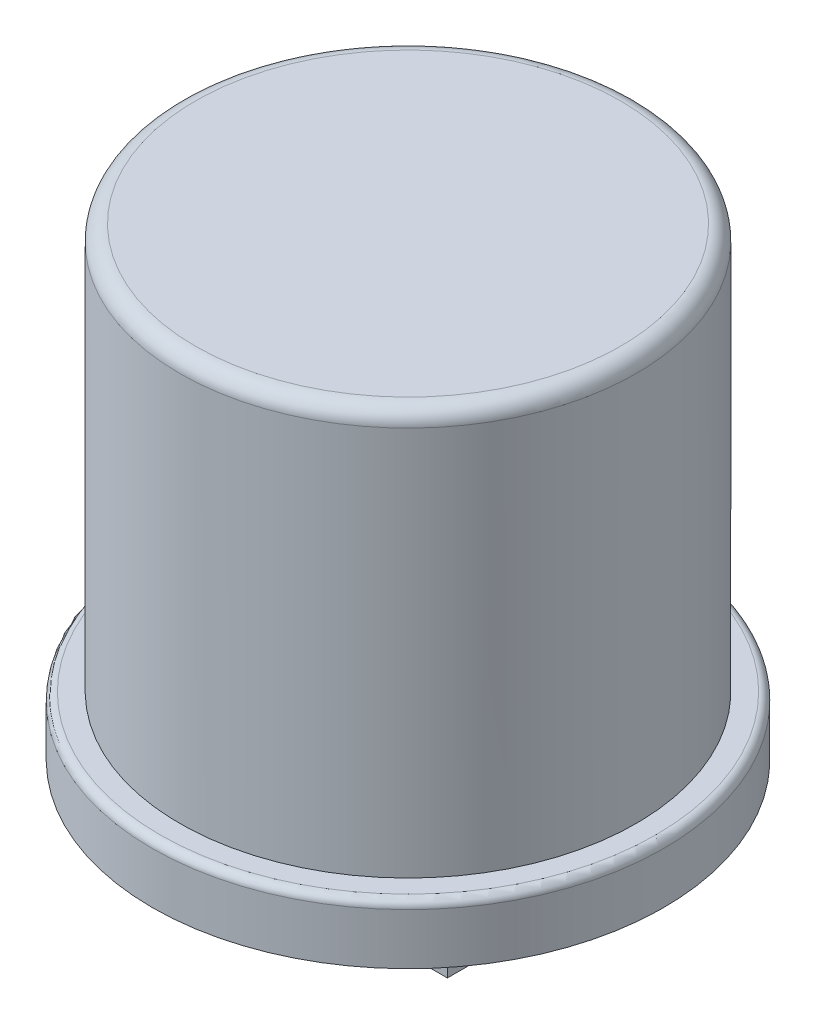
SolidWorks part; units mm, degrees
ref_plane "Front Plane" through (0, 0, 0) normal (0, 0, 1) x (1, 0, 0)
ref_plane "Top Plane" through (0, 0, 0) normal (0, 1, 0) x (1, 0, 0)
ref_plane "Right Plane" through (0, 0, 0) normal (1, 0, 0) x (0, 0, -1)
sketch "Sketch1" plane through (0, 0, 0) normal (0, 1, 0) x (1, 0, 0)
  circle A0 centre (0, 0) radius 6.5
  dimension "D1" = 13
extrude "Boss-Extrude1" add sketch "Sketch1" along normal blind 1.5
sketch "Sketch2" plane through (0, 1.5, 0) normal (0, 1, 0) x (1, 0, 0)
  circle A0 centre (0, 0) radius 5.8
  dimension "D1" = 11.6
extrude "Boss-Extrude2" add sketch "Sketch2" along normal blind 10.3
fillet "Fillet1" radius 0.4 1 edges at (0, 11.8, 5.8)
sketch "Sketch3" plane through (0, 0, 0) normal (0, -1, 0) x (1, 0, 0)
  circle A0 centre (0, 0) radius 5
  dimension "D1" = 10
extrude "Cut-Extrude1" cut sketch "Sketch3" against normal blind 4.8
sketch "Sketch4" plane through (0, 4.8, 0) normal (0, -1, 0) x (1, 0, 0)
  line L0 (-4.991, 0.3) -> (-2.9, 0.3)
  line L1 (-4.991, -0.3) -> (-2.9, -0.3)
  line L2 (-5, 0) -> (5, 0) construction
  line L3 (-2.9, 0.3) -> (-2.9, -0.3)
  line L4 (0, -0.825) -> (0, 0.825) construction
  line L5 (2.9, 0.3) -> (2.9, -0.3)
  line L6 (4.991, -0.3) -> (2.9, -0.3)
  line L7 (4.991, 0.3) -> (2.9, 0.3)
  line L8 (0, 5) -> (0, -5) construction
  line L9 (-0.3, 4.991) -> (-0.3, 2.7)
  line L10 (0.3, 4.991) -> (0.3, 2.7)
  line L11 (0.3, 2.7) -> (-0.3, 2.7)
  line L12 (0.3, -2.7) -> (-0.3, -2.7)
  line L13 (0.3, -4.991) -> (0.3, -2.7)
  line L14 (-0.3, -4.991) -> (-0.3, -2.7)
  circle A0 centre (0, 0) radius 5 construction
  circle A1 centre (0, 0) radius 5 construction
  arc A2 (-0.3, -4.991) -> (0.3, -4.991) centre (0, 0) ccw
  circle A3 centre (0, 0) radius 5
  arc A4 (-4.991, 0.3) -> (-4.991, -0.3) centre (0, 0) ccw
  arc A5 (4.991, -0.3) -> (4.991, 0.3) centre (0, 0) ccw
  arc A6 (0.3, 4.991) -> (-0.3, 4.991) centre (0, 0) ccw
  point P11 (-2.9, 0)
  point P25 (0, 2.7)
  dimension "D1" = 5.8
  dimension "D2" = 0.6
  dimension "D3" = 5.4
  dimension "D4" = 0
extrude "Boss-Extrude3" add sketch "Sketch4" along normal up to surface (4.8 mm away) up to face at (0, 0, -5)
sketch "Sketch5" plane through (0, 4.8, 0) normal (0, -1, 0) x (1, 0, 0)
  line L0 (-2.9, 0.3) -> (-2.9, -0.3) construction
  line L1 (-1, 2.7) -> (1, 2.7)
  line L2 (-1, 2.7) -> (-1, 1.9)
  line L3 (-1, 1.9) -> (1, 1.9)
  line L4 (1, 2.7) -> (1, 1.9)
  line L5 (-2.9, 1.9) -> (-1.9, 1.9)
  line L6 (-2.9, 1.9) -> (-2.9, -1.9)
  line L7 (-2.9, -1.9) -> (-1.9, -1.9)
  line L8 (-1.9, 1.9) -> (-1.9, -1.9)
  line L9 (0.3, 2.7) -> (-0.3, 2.7) construction
  line L10 (0, -0.825) -> (0, 0.825) construction
  line L11 (1.9, 1.9) -> (1.9, -1.9)
  line L12 (2.9, -1.9) -> (1.9, -1.9)
  line L13 (2.9, 1.9) -> (2.9, -1.9)
  line L14 (2.9, 1.9) -> (1.9, 1.9)
  line L15 (0.825, 0) -> (-0.825, 0) construction
  line L16 (1, -2.7) -> (1, -1.9)
  line L17 (-1, -1.9) -> (1, -1.9)
  line L18 (-1, -2.7) -> (-1, -1.9)
  line L19 (-1, -2.7) -> (1, -2.7)
  point P4 (0, 2.7)
  point P10 (-1.9, 0)
  dimension "D1" = 3.8
  dimension "D2" = 2
  dimension "D3" = 1
extrude "Boss-Extrude4" add sketch "Sketch5" along normal blind 7.2
sketch "Sketch6" plane through (0, 0, 1.9) normal (0, 0, 1) x (1, 0, 0)
  line L0 (-1.9, -1.4) -> (-1.6, -1.7)
  line L1 (-1.9, -2.4) -> (-1.9, 4.8) construction
  line L2 (-1.6, -1.7) -> (-2.4, -2.4)
  line L3 (-1.9, -2.4) -> (-2.9, -2.4) construction
  line L4 (-2.9, -2.4) -> (-2.9, 4.8) construction
  line L5 (-1.9, -1.4) -> (-1.9, -2.4)
  line L6 (-1.9, -2.4) -> (-2.4, -2.4)
  line L7 (0, -0.825) -> (0, 0.825) construction
  line L8 (1.9, -2.4) -> (2.4, -2.4)
  line L9 (1.9, -1.4) -> (1.9, -2.4)
  line L10 (1.6, -1.7) -> (2.4, -2.4)
  line L11 (1.9, -1.4) -> (1.6, -1.7)
  line M2 (1.9, 4.8) -> (1.9, -2.4)
  line M3 (1.9, -2.4) -> (2.9, -2.4)
  dimension "D1" = 1.3
  dimension "D2" = 1
  dimension "D3" = 0.7
extrude "Cut-Extrude2" cut sketch "Sketch6" against normal up to next contours L6 L5 L2 | L10 L9 M3 region at (-2.0667, -2.2542, 1.9) region at (2.0667, -2.2542, 1.9)
extrude "Boss-Extrude5" add sketch "Sketch6<3>" against normal up to surface (3.8 mm away) contours L0 L5 L2 | L11 L10 M2 region at (-1.8, -1.6875, 1.9) region at (1.8, -1.6875, 1.9) up to face at (2.4, 0.5675, -1.9)
sketch "Sketch6<3>" plane through (0, 0, 1.9) normal (0, 0, 1) x (1, 0, 0) same geometry as "Sketch6"
fillet "Fillet2" radius 0.1 2 edges at (1.6, -1.7, 0) (-1.6, -1.7, 0)
fillet "Fillet3" radius 0.2 1 edges at (0, 1.5, 6.5)
